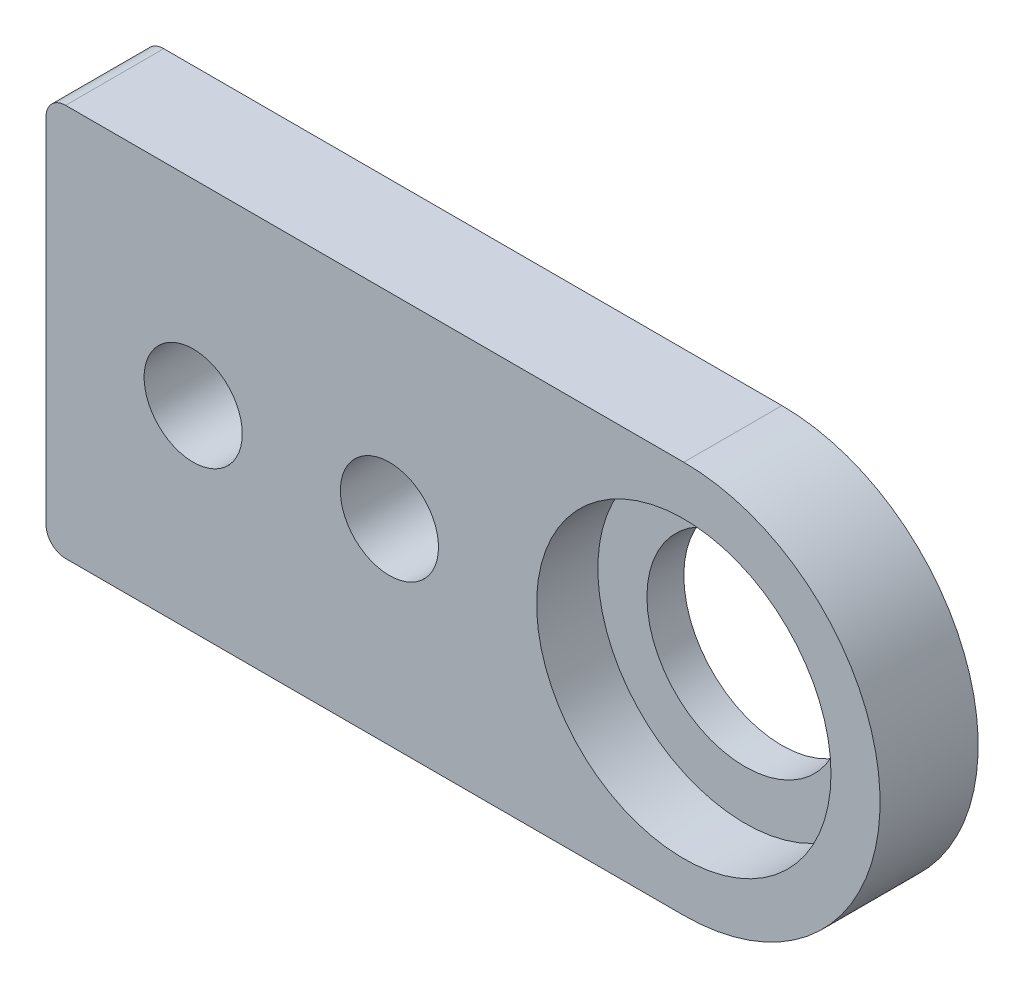
SolidWorks part; units mm, degrees
ref_plane "Front Plane" through (0, 0, 0) normal (0, 0, 1) x (1, 0, 0)
ref_plane "Top Plane" through (0, 0, 0) normal (0, 1, 0) x (1, 0, 0)
ref_plane "Right Plane" through (0, 0, 0) normal (1, 0, 0) x (0, 0, -1)
sketch "Sketch1" plane through (0, 0, 0) normal (0, 0, 1) x (1, 0, 0)
  line L0 (0, -12.7) -> (53.975, -12.7) construction
  line L1 (0, -25.4) -> (53.975, -25.4)
  line L2 (0, -25.4) -> (0, 0)
  line L3 (0, 0) -> (53.975, 0)
  line L4 (53.975, -25.4) -> (53.975, 0)
  circle A0 centre (41.275, -12.7) radius 9.525
  circle A1 centre (41.275, -12.7) radius 6.35
  circle A2 centre (9.525, -12.7) radius 3.175
  circle A3 centre (22.225, -12.7) radius 3.175
  point P0 (41.275, -12.7)
  dimension "D2" = 19.05
  dimension "D3" = 12.7
  dimension "D5" = 6.35
  dimension "D1" = 25.4
  dimension "D6" = 12.7
  dimension "D7" = 19.05
  dimension "D8" = 12.7
  dimension "D9" = 9.525
extrude "Boss-Extrude2" add sketch "Sketch1" along normal blind 6.35 contours L1 L4 L3 L2 A3 A2 A0 | L0 L2 L1 L4 A0 A3 A2 region at (23.6935, -5.397, 0) region at (23.6935, -20.003, 0)
extrude "Boss-Extrude3" add sketch "Sketch1<5>" along normal blind 2.3876 contours A0 A1 | L0 A0 A1 region at (41.275, -6.137, 0) region at (49.2125, -12.913, 0)
sketch "Sketch1<5>" plane through (0, 0, 0) normal (0, 0, 1) x (1, 0, 0) same geometry as "Sketch1"
fillet "Fillet1" radius 1.27 4 edges at (0, -25.4, 3.175) (0, 0, 3.175) (53.975, -25.4, 3.175) (53.975, 0, 3.175)
sketch "Sketch2" plane through (0, 0, 6.35) normal (0, 0, 1) x (1, 0, 0)
  line L0 (1.27, 0) -> (52.705, 0) construction
  line L1 (28.575, -25.4) -> (53.975, -25.4)
  line L2 (28.575, -25.4) -> (28.575, 0)
  line L3 (28.575, 0) -> (53.975, 0)
  line L4 (53.975, -25.4) -> (53.975, 0)
  line L5 (28.575, -25.4) -> (53.975, 0) construction
  line L6 (28.575, 0) -> (53.975, -25.4) construction
  circle A0 centre (41.275, -12.7) radius 12.7
  point P0 (41.275, -12.7)
  arc M12 (52.705, -25.4) -> (53.975, -24.13) centre (52.705, -24.13) ccw
  line M13 (53.975, -24.13) -> (53.975, -1.27)
  arc M14 (53.975, -1.27) -> (52.705, 0) centre (52.705, -1.27) ccw
  line M15 (52.705, 0) -> (1.27, 0)
extrude "Cut-Extrude1" cut sketch "Sketch2" against normal through all contours A0 L4 M14 M15 | A0 L1 M12 M13 region at (51.1124, -22.5374, 6.35) region at (51.1124, -2.8626, 6.35)
